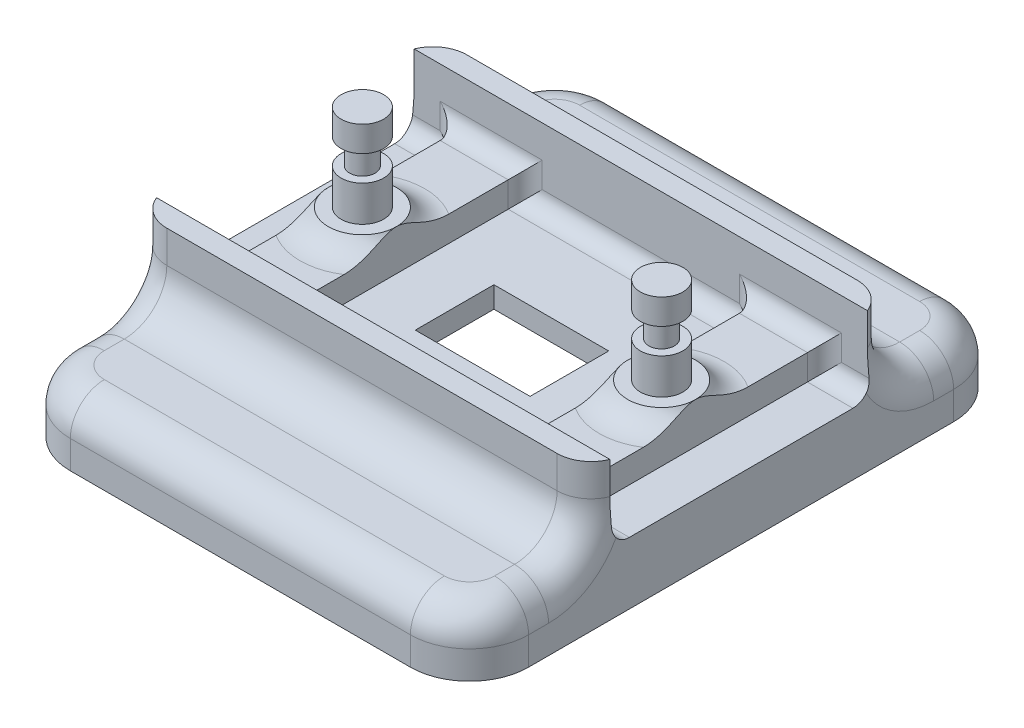
SolidWorks part; units mm, degrees
ref_plane "Alzado" through (0, 0, 0) normal (0, 0, 1) x (1, 0, 0)
ref_plane "Planta" through (0, 0, 0) normal (0, 1, 0) x (1, 0, 0)
ref_plane "Vista lateral" through (0, 0, 0) normal (1, 0, 0) x (0, 0, -1)
sketch "Croquis1" plane through (0, 0, 0) normal (0, 1, 0) x (1, 0, 0)
  line L9 (20, -30) -> (-20, -30)
  line L10 (25, -25) -> (25, 25)
  line L11 (20, 30) -> (-20, 30)
  line L12 (-25, -25) -> (-25, 25)
  line L13 (25, -30) -> (-25, 30) construction
  line L14 (25, 30) -> (-25, -30) construction
  arc A4 (20, -30) -> (25, -25) centre (20, -25) ccw
  arc A5 (-25, -25) -> (-20, -30) centre (-20, -25) ccw
  arc A6 (25, 25) -> (20, 30) centre (20, 25) ccw
  arc A7 (-20, 30) -> (-25, 25) centre (-20, 25) ccw
  point P0 (0, 0)
  dimension "D3" = 5
  dimension "D1" = 60
  dimension "D2" = 50
sketch "Croquis2" plane through (0, 0, 0) normal (0, 1, 0) x (1, 0, 0)
  line L4 (20, 31.95) -> (-20, 31.95)
  line L5 (-26.95, 25) -> (-26.95, -25)
  line L6 (-20, -31.95) -> (20, -31.95)
  line L7 (26.95, -25) -> (26.95, 25)
  line L8 (20, 29.95) -> (-20, 29.95)
  line L9 (-24.95, 25) -> (-24.95, -25)
  line L10 (-20, -29.95) -> (20, -29.95)
  line L11 (24.95, -25) -> (24.95, 25)
  line L12 (20, 29.95) -> (-20, 29.95)
  line L13 (-24.95, 25) -> (-24.95, -25)
  line L14 (-20, -29.95) -> (20, -29.95)
  line L15 (24.95, -25) -> (24.95, 25)
  arc A4 (-20, 31.95) -> (-26.95, 25) centre (-20, 25) ccw
  arc A5 (-26.95, -25) -> (-20, -31.95) centre (-20, -25) ccw
  arc A6 (20, -31.95) -> (26.95, -25) centre (20, -25) ccw
  arc A7 (26.95, 25) -> (20, 31.95) centre (20, 25) ccw
  arc A8 (-20, 29.95) -> (-24.95, 25) centre (-20, 25) ccw
  arc A9 (-24.95, -25) -> (-20, -29.95) centre (-20, -25) ccw
  arc A10 (20, -29.95) -> (24.95, -25) centre (20, -25) ccw
  arc A11 (24.95, 25) -> (20, 29.95) centre (20, 25) ccw
  arc A12 (-20, 29.95) -> (-24.95, 25) centre (-20, 25) ccw
  arc A13 (-24.95, -25) -> (-20, -29.95) centre (-20, -25) ccw
  arc A14 (20, -29.95) -> (24.95, -25) centre (20, -25) ccw
  arc A15 (24.95, 25) -> (20, 29.95) centre (20, 25) ccw
  dimension "D1" = 0.05
  dimension "D2" = 2
extrude "Saliente-Extruir1" add sketch "Croquis2" along normal blind 2.5 contours L15 A15 L12 A12 L13 A13 L14 A14 | L7 A7 L4 A4 L5 A5 L6 A6 A15 L15 A14 L14 A13 L13 A12 L12 region at (24.3233, 0, -29.3233) region at (0, 0, 0)
extrude "Saliente-Extruir2" add sketch "Croquis2<3>" against normal blind 4.8
sketch "Croquis2<3>" plane through (0, 0, 0) normal (0, 1, 0) x (1, 0, 0) same geometry as "Croquis2"
fillet "Redondeo1" radius 1 8 edges at (0, 0, 29.95) (-23.5002, 0, 28.5002) (-24.95, 0, 0) (-23.5002, 0, -28.5002) (0, 0, -29.95) (23.5002, 0, -28.5002) (24.95, 0, 0) (23.5002, 0, 28.5002)
sketch "Croquis3" plane through (0, 2.5, 0) normal (0, 1, 0) x (1, 0, 0)
  line L0 (-26.95, 25) -> (-26.95, -25) construction
  line L1 (0, 0) -> (-26.95, 0) construction
  line L2 (25, 30) -> (-25, -30) construction
  line L3 (-26.95, 15.15) -> (-26.95, -15.15) construction
  line L4 (-26.95, 15.15) -> (26.95, 15.15)
  line L5 (26.95, -25) -> (26.95, 25) construction
  line L6 (-26.95, 15.15) -> (-26.95, 17.65)
  line L7 (-26.95, 17.65) -> (26.95, 17.65)
  line L8 (26.95, 17.65) -> (26.95, 15.15)
  line L9 (26.95, -17.65) -> (26.95, -15.15)
  line L10 (-26.95, -15.15) -> (-26.95, -17.65)
  line L11 (-26.95, -17.65) -> (26.95, -17.65)
  line L12 (-26.95, -15.15) -> (26.95, -15.15)
  line L13 (0, 0) -> (0, 15.15) construction
  line L14 (-21.6, -15.15) -> (-21.6, 15.15)
  line L15 (-13.6, -15.15) -> (-13.6, 15.15)
  line L16 (21.6, -15.15) -> (21.6, 15.15)
  line L17 (13.6, -15.15) -> (13.6, 15.15)
  circle A0 centre (-17.6, 0) radius 1.625
  circle A1 centre (-17.6, 0) radius 4
  circle A2 centre (17.6, 0) radius 1.625
  circle A3 centre (17.6, 0) radius 4
  point P9 (-26.95, 0)
  point P17 (-17.6, 0)
  point P27 (-13.6, 0)
  point P28 (-21.6, 0)
  line M16 (26.95, -25) -> (26.95, 25)
  line M20 (-26.95, 25) -> (-26.95, -25)
  dimension "D4" = 3.25
  dimension "D5" = 8
  dimension "D1" = 30.3
  dimension "D2" = 2.5
  dimension "D3" = 9.35
extrude "Saliente-Extruir3" add sketch "Croquis3" along normal blind 8.8 contours L7 L4 M20 M16 | L12 L11 M20 M16 region at (0, 2.5, -16.4) region at (0, 2.5, 16.4)
extrude "Saliente-Extruir6" add sketch "Croquis3<3>" along normal blind 3 contours A1 L15 L4 L14 | L17 A3 L16 L4 | L16 A3 L17 L12 | A1 L14 L12 L15 | A1 A0 | A3 A2 region at (-17.6, 2.5, -9.1126) region at (-17.6, 2.5, 9.1126) region at (-17.6, 2.5, -3.8869) region at (17.6, 2.5, -9.1126) region at (17.6, 2.5, 9.1126) region at (17.6, 2.5, -3.8869)
sketch "Croquis3<3>" plane through (0, 2.5, 0) normal (0, 1, 0) x (1, 0, 0) same geometry as "Croquis3"
extrude "Saliente-Extruir7" add sketch "Croquis3<4>" along normal blind 4.8 contours A1 A0 | A3 A2 region at (-17.6, 2.5, -3.8869) region at (17.6, 2.5, -3.8869)
sketch "Croquis3<4>" plane through (0, 2.5, 0) normal (0, 1, 0) x (1, 0, 0) same geometry as "Croquis3"
fillet "Redondeo2" radius 2 18 edges at (17.6, 5.5, 15.15) (21.6, 4, 15.15) (24.275, 2.5, 15.15) (-24.275, 2.5, 15.15) (-21.6, 4, 15.15) (-17.6, 5.5, 15.15) (-13.6, 4, 15.15) (0, 2.5, 15.15) (13.6, 4, 15.15) (-13.6, 4, -15.15) (-17.6, 5.5, -15.15) (-21.6, 4, -15.15) (-24.275, 2.5, -15.15) (24.275, 2.5, -15.15) (21.6, 4, -15.15) (17.6, 5.5, -15.15) (13.6, 4, -15.15) (0, 2.5, -15.15)
fillet "Redondeo3" radius 5 2 edges at (0, 2.5, 17.65) (0, 2.5, -17.65)
fillet "Redondeo4" radius 4 2 edges at (-17.6, 5.5, -4) (17.6, 5.5, -4)
fillet "Redondeo5" radius 4 18 edges at (26.95, 9.4, -17.65) (26.95, 3.9645, -19.1145) (26.95, 2.5, -23.825) (-26.95, 9.4, -17.65) (-26.95, 3.9645, -19.1145) (-26.95, 2.5, -23.825) (-24.9144, 2.5, -29.9144) (0, 2.5, -31.95) (-26.95, 9.4, 17.65) (-26.95, 3.9645, 19.1145) (-26.95, 2.5, 23.825) (-24.9144, 2.5, 29.9144) (0, 2.5, 31.95) (26.95, 9.4, 17.65) (26.95, 3.9645, 19.1145) (26.95, 2.5, 23.825) (24.9144, 2.5, -29.9144) (24.9144, 2.5, 29.9144)
sketch "Croquis4" plane through (0, 2.5, 0) normal (0, 1, 0) x (1, 0, 0)
  circle A0 centre (-17.6, 0) radius 2.5
  circle A1 centre (17.6, 0) radius 2.5
  dimension "D1" = 5
extrude "Saliente-Extruir8" add sketch "Croquis4" along normal blind 15
sketch "Croquis5" plane through (0, 17.5, 0) normal (0, 1, 0) x (1, 0, 0)
  circle A0 centre (-17.6, 0) radius 1.5
  circle A1 centre (17.6, 0) radius 2.5
  circle A2 centre (17.6, 0) radius 2.5
  circle A3 centre (-17.6, 0) radius 2.5
  circle A4 centre (-17.6, 0) radius 2.5
  circle A5 centre (17.6, 0) radius 1.5
  dimension "D1" = 0
  dimension "D2" = 0
  dimension "D3" = 1
extrude "Cortar-Extruir1" cut sketch "Croquis5" against normal blind 3 from offset 3 offset against normal yes
sketch "Croquis6" plane through (0, 2.5, 0) normal (0, 1, 0) x (1, 0, 0)
  line L0 (6.75, -4.625) -> (-6.75, -4.625)
  line L1 (6.75, -4.625) -> (6.75, 4.625)
  line L2 (6.75, 4.625) -> (-6.75, 4.625)
  line L3 (-6.75, -4.625) -> (-6.75, 4.625)
  point P4 (0, 4.625)
  point P6 (6.75, 0)
  dimension "D1" = 13.5
  dimension "D2" = 9.25
extrude "Cortar-Extruir2" cut sketch "Croquis6" against normal through all
